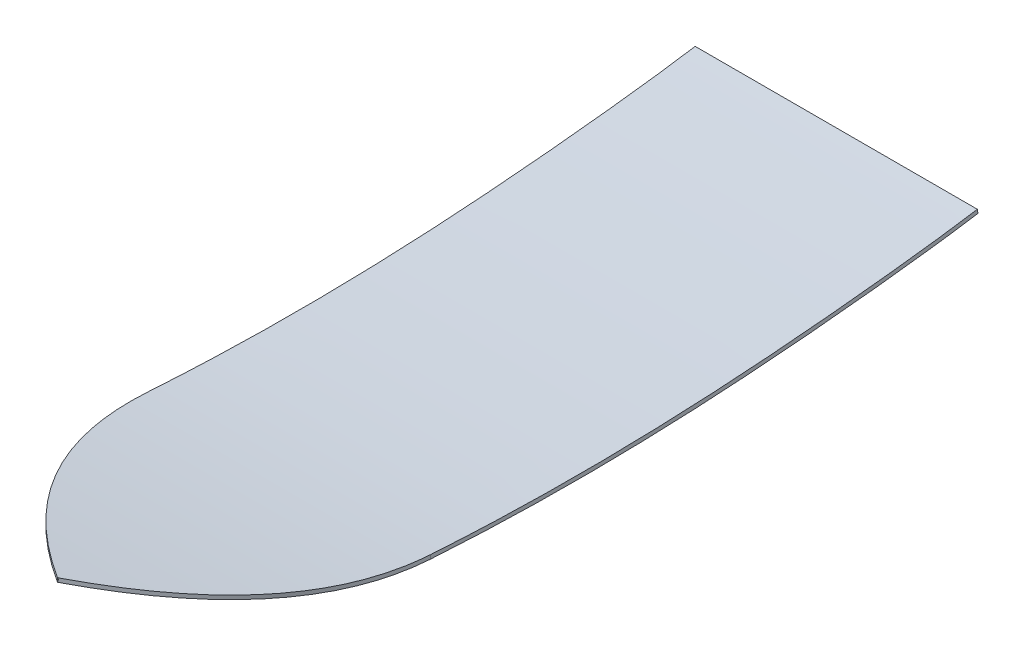
SolidWorks part; units mm, degrees
ref_plane "Front Plane" through (0, 0, 0) normal (0, 0, 1) x (1, 0, 0)
ref_plane "Top Plane" through (0, 0, 0) normal (0, 1, 0) x (1, 0, 0)
ref_plane "Right Plane" through (0, 0, 0) normal (1, 0, 0) x (0, 0, -1)
sketch "Sketch1" plane through (0, 0, 0) normal (1, 0, 0) x (0, 0, -1)
  line L18 (-3738.5983, 39.9762) -> (-3742.2555, 15.2452)
  line L19 (1224.8959, 42.2022) -> (1228.9146, 17.5273)
  spline S0 degree 3 poles (-3738.5983, 39.9762) (-3676.6668, 30.8179) (-3580.8196, 17.0127) (-3418.1852, -5.3366) (-3285.2654, -22.6294) (-3122.3189, -42.5643) (-2963.2971, -60.7391) (-2780.4099, -79.6431) (-2606.2858, -95.7337) (-2475.5086, -106.4069) (-2396.7196, -112.2763) (-2370.5253, -114.1623) (-2341.1566, -116.2579) (-2314.5669, -118.0922) (-2237.9, -123.1863) (-2134.3792, -129.4952) (-1987.6646, -136.9627) (-1843.6769, -142.8638) (-1701.4987, -147.2965) (-1513.3027, -151.3349) (-1278.9063, -152.978) (-1041.5569, -150.1315) (-847.5049, -145.0321) (-699.2339, -139.7322) (-547.5231, -132.8724) (-417.564, -125.7619) (-311.0449, -119.1673) (-229.6626, -113.7364) (-92.901, -103.9688) (73.1857, -90.6476) (265.6327, -73.3183) (427.7267, -57.4995) (637.3896, -35.4773) (931.3071, -1.1683) (1130.7126, 26.8629) (1224.8959, 42.2022) knots 0.002322 0.002322 0.002322 0.002322 0.03125 0.046875 0.078125 0.09375 0.125 0.15625 0.1875 0.21875 0.230469 0.233887 0.234375 0.248047 0.25 0.28125 0.3125 0.34375 0.375 0.40625 0.46875 0.53125 0.5625 0.59375 0.625 0.65625 0.671875 0.6875 0.703125 0.75 0.78125 0.8125 0.84375 0.90625 1 1 1 1
  spline S1 degree 1 poles (-3742.2555, 15.2452) (1228.9146, 17.5273) knots 0 0 1 1 construction
  spline S2 degree 3 poles (-3742.2555, 15.2452) (-3725.5351, 12.7726) (-3692.1084, 7.8643) (-3625.0811, -1.8347) (-3541.2259, -13.6923) (-3440.8329, -27.4197) (-3307.8155, -44.9601) (-3144.0097, -65.3131) (-2953.852, -86.9087) (-2771.6608, -105.6136) (-2627.128, -118.8728) (-2515.9482, -128.1875) (-2434.7442, -134.559) (-2355.7134, -140.3461) (-2278.7245, -145.5872) (-2202.96, -150.3601) (-2103.4366, -156.1261) (-1981.3894, -162.2745) (-1837.6009, -168.0968) (-1695.5745, -172.4587) (-1554.5436, -175.4234) (-1413.8227, -177.031) (-1272.8067, -177.2886) (-1130.8857, -176.2027) (-987.4643, -173.7407) (-841.9463, -169.8704) (-693.6865, -164.5269) (-567.2651, -158.7757) (-464.0047, -153.3393) (-385.3944, -148.8271) (-305.4956, -143.8614) (-224.1326, -138.4132) (-142.1316, -132.5398) (-32.1561, -124.179) (105.9053, -112.8132) (270.6315, -97.9581) (432.4724, -82.1458) (589.4617, -65.6413) (714.5832, -51.5357) (810.2534, -40.1784) (879.5418, -31.6584) (946.1151, -23.171) (1009.7254, -14.7509) (1060.0588, -7.8192) (1098.5974, -2.3421) (1126.6066, 1.7274) (1153.6906, 5.7542) (1175.4645, 9.0709) (1192.3902, 11.6987) (1204.8358, 13.6565) (1214.9908, 15.2758) (1222.9965, 16.5658) (1226.9369, 17.2052) (1228.9146, 17.5273) knots 0.002322 0.002322 0.002322 0.002322 0.010116 0.01791 0.033499 0.049088 0.064677 0.095854 0.127032 0.158209 0.189386 0.204975 0.220564 0.236153 0.251741 0.26733 0.282919 0.314096 0.345274 0.376451 0.407629 0.438806 0.469983 0.501161 0.532338 0.563516 0.594693 0.625871 0.641459 0.657048 0.672637 0.688226 0.703814 0.719403 0.75058 0.781758 0.812935 0.844113 0.87529 0.890879 0.906468 0.922056 0.937645 0.953234 0.961028 0.968823 0.976617 0.984411 0.988308 0.992206 0.996103 0.998051 1 1 1 1
  dimension "D1" = 25
extrude "Boss-Extrude1" add sketch "Sketch1" along normal blind 1524 and the other way blind 1524
sketch "Sketch3" plane through (0, 0, 0) normal (0, 1, 0) x (1, 0, 0)
  line L0 (-900, 1254.9805) -> (900, 1254.9805)
  line L1 (-900, 1254.9805) -> (-900, -2262.5532)
  line L2 (900, 1254.9805) -> (900, -2262.5532)
  line L3 (0, 2955.5244) -> (0, -2061.9995) construction
  line L4 (-2934.2017, 4085.2419) -> (2797.2556, 4085.2419)
  line L5 (-2934.2017, 4085.2419) -> (-2934.2017, -3918.064)
  line L6 (-2934.2017, -3918.064) -> (2797.2556, -3918.064)
  line L7 (2797.2556, 4085.2419) -> (2797.2556, -3918.064)
  line L8 (-94.9374, 0) -> (0, 0) construction
  line L11 (-1524, 1954.9582) -> (1524, 1954.9582) construction
  spline S0 degree 2 poles (-900, -2262.5532) (-900, -3137.1918) (0, -3742.2555) knots 0 0 0 1 1 1
  spline S1 degree 2 poles (900, -2262.5532) (900, -3137.1918) (0, -3742.2555) knots 0 0 0 1 1 1
  dimension "D1" = 1800
extrude "Cut-Extrude1" cut sketch "Sketch3" against normal through all both and the other way through all
